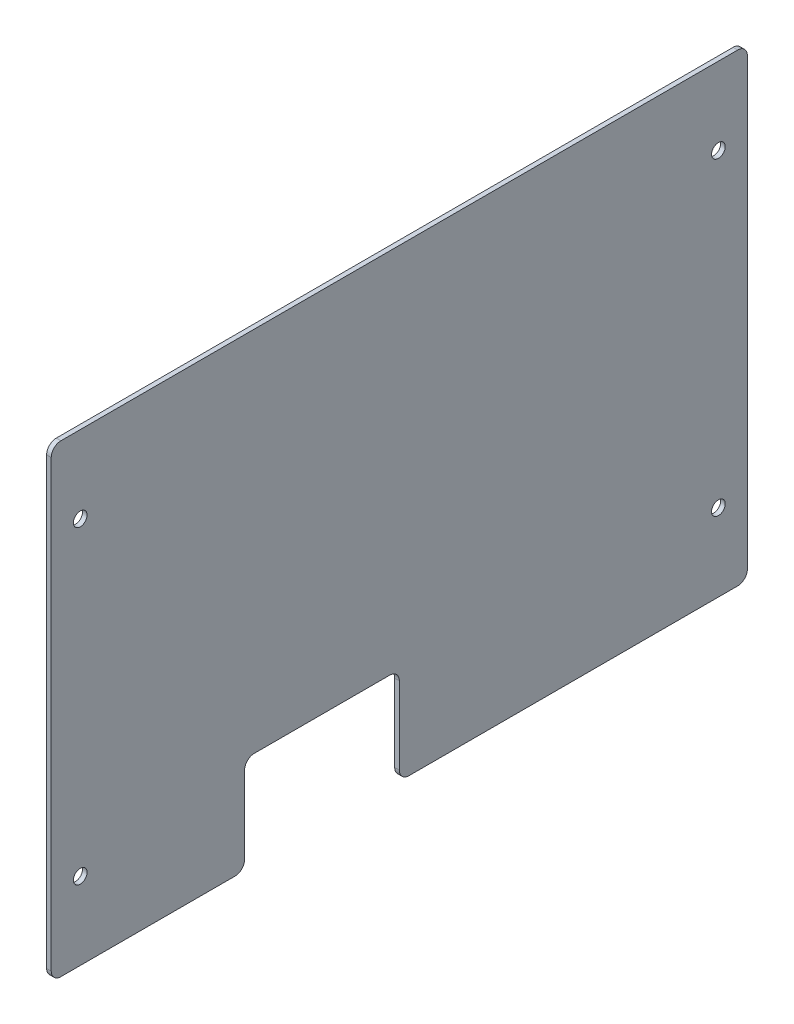
SolidWorks part; units mm, degrees
material "Low Carbon Steel"
ref_plane "Front Plane" through (0, 0, 0) normal (0, 0, 1) x (1, 0, 0)
ref_plane "Top Plane" through (0, 0, 0) normal (0, 1, 0) x (1, 0, 0)
ref_plane "Right Plane" through (0, 0, 0) normal (1, 0, 0) x (0, 0, -1)
sketch "Sketch1" plane through (0, 0, 0) normal (1, 0, 0) x (0, 0, -1)
  line L0 (-107.95, -152.4) -> (-222.25, -152.4)
  line L1 (222.25, -152.4) -> (6.35, -152.4)
  line L2 (228.6, -146.05) -> (228.6, 146.05)
  line L3 (222.25, 152.4) -> (-222.25, 152.4)
  line L4 (-228.6, -146.05) -> (-228.6, 146.05)
  line L5 (228.6, -152.4) -> (-228.6, 152.4) construction
  line L6 (228.6, 152.4) -> (-228.6, -152.4) construction
  line L8 (-101.6, -146.05) -> (-101.6, -95.25)
  line L9 (-95.25, -88.9) -> (-6.35, -88.9)
  line L10 (0, -146.05) -> (0, -95.25)
  arc A0 (222.25, 152.4) -> (228.6, 146.05) centre (222.25, 146.05) cw
  arc A1 (228.6, -146.05) -> (222.25, -152.4) centre (222.25, -146.05) cw
  arc A2 (-222.25, -152.4) -> (-228.6, -146.05) centre (-222.25, -146.05) cw
  arc A3 (-228.6, 146.05) -> (-222.25, 152.4) centre (-222.25, 146.05) cw
  arc A4 (-107.95, -152.4) -> (-101.6, -146.05) centre (-107.95, -146.05) ccw
  arc A5 (-101.6, -95.25) -> (-95.25, -88.9) centre (-95.25, -95.25) cw
  arc A6 (-6.35, -88.9) -> (0, -95.25) centre (-6.35, -95.25) cw
  arc A7 (0, -146.05) -> (6.35, -152.4) centre (6.35, -146.05) ccw
  point P0 (0, 0)
  point P27 (-101.6, -152.4)
  dimension "D3" = 6.35
  dimension "D7" = 6.35
  dimension "D1" = 304.8
  dimension "D2" = 457.2
  dimension "D4" = 101.6
  dimension "D5" = 101.6
  dimension "D6" = 63.5
base flange "Base-Flange1" sketch "Sketch1" thickness 3.0378 reverse thickness direction no parameters "D1"=3.175
hole_wizard "M8 Clearance Hole1" positions "Sketch6" profile "Sketch7" hole size "M8" standard "Peddi DIN" end condition through all
sketch "Sketch6" plane through (0, 0, 0) normal (1, 0, 0) x (0, 0, -1)
  line L0 (209.55, 101.6) -> (-209.55, 101.6) construction
  line L3 (0, 0) -> (0, 101.6) construction
  point P0 (-209.55, 101.6)
  point P2 (-209.55, -101.6)
  point P4 (209.55, -101.6)
  point P6 (209.55, 101.6)
  dimension "D1" = 419.1
  dimension "D2" = 203.2
  dimension "D3" = 101.6
sketch "Sketch7" plane through (0, 101.6, 209.55) normal (0, 1, 0) x (0, 0, -1)
  line L0 (0, 0) -> (0, 3.0378)
  line L1 (0, 3.0378) -> (4.5, 3.0378)
  line L2 (4.5, 3.0378) -> (4.5, 0)
  line L5 (4.5, 0) -> (0, 0)
  line L11 (0, -6.35) -> (0, 107.95) construction
  dimension "Thru Hole Dia." = 9
  dimension "Thru Hole Depth" = 3.0378
other "Freeze***"
sketch "Bend-Lines1" [suppressed] plane through (0, 0, 0) normal (0, 1, 0) x (1, 0, 0)
sketch "Bounding-Box1" [suppressed] plane through (0, 0, 0) normal (0, 1, 0) x (1, 0, 0)
sheet metal parameters "Sheet-Metal1" thickness 3.0378 parameters "D1"=3.175
flat pattern "Flat-Pattern1" [suppressed]
sketch "Bend-Lines2" plane through (0, 0, 0) normal (0, 1, 0) x (1, 0, 0)
sketch3d "Bounding-Box2" [suppressed]
  line L0 (6.35, 6.3501, 0) -> (-450.85, 6.35, 0) construction
  line L1 (6.35, -158.7499, 0) -> (-450.85, -158.75, 0) construction
  line L2 (6.35, 6.3501, 0) -> (6.35, -158.7499, 0) construction
  line L3 (-450.85, 6.35, 0) -> (-450.85, -158.75, 0) construction
sheet metal parameters "Sheet-Metal2" thickness 3.0378 parameters "D1"=3.175
flat pattern "Flat-Pattern1"
sketch "Bend-Lines2"
sketch3d "Bounding-Box2" [suppressed]
  line L0 (6.3499, 6.3501, 0) -> (-450.85, 6.35, 0) construction
  line L1 (6.35, -298.4499, 0) -> (-450.8499, -298.45, 0) construction
  line L2 (6.3499, 6.3501, 0) -> (6.35, -298.4499, 0) construction
  line L3 (-450.85, 6.35, 0) -> (-450.8499, -298.45, 0) construction
equation "\"D3@Sketch6\"=\"D2@Sketch6\"/2"
